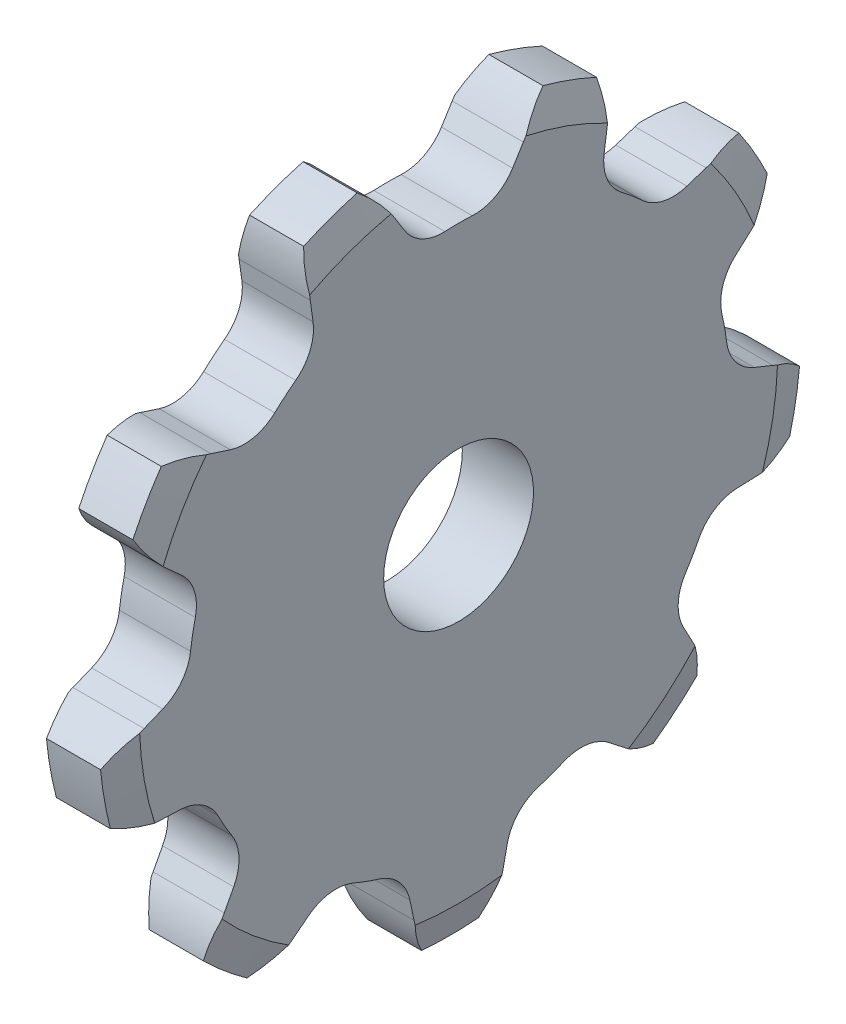
SolidWorks part; units mm, degrees
ref_plane "Plane1" through (0, 0, 0) normal (0, 0, 1) x (1, 0, 0)
ref_plane "Plane2" through (0, 0, 0) normal (0, 1, 0) x (1, 0, 0)
ref_plane "Plane3" through (0, 0, 0) normal (1, 0, 0) x (0, 0, -1)
sketch "Clipboard" plane through (0, 0, 0) normal (0, 1, 0) x (1, 0, 0)
  line L0 (0, 0) -> (75.2619, -11.9203)
  line L1 (-15, 0) -> (100, 0) construction
  line L2 (0, 0) -> (-2.1039, 2.3779)
  line L3 (0, 0) -> (-11.863, 4.5341)
  line L4 (0, 0) -> (8.5297, 1.351)
  line L5 (0, 0) -> (-71.3958, -26.6285)
  line L6 (0, 0) -> (-20.0029, -13.496)
  line L7 (-2.1039, 2.3779) -> (14.2981, 76.7917)
  line L8 (-76.2, 54.61) -> (-19.7358, 54.61)
  line L9 (-66.6514, 23.5599) -> (-48.0177, 27.5206)
  line L10 (-76.2, 71.12) -> (35.1969, 71.12)
  line L11 (0, 0) -> (-25.4, 0)
  line L12 (-76.2, 101.6) -> (-47.498, 101.6)
  circle A0 centre (0, 0) radius 19.05
  circle A1 centre (0, 0) radius 25.4
  circle A2 centre (0, 0) radius 25.4
  dimension "Num_teeth" = 9
  dimension "Pitch_radius" = 111.3969
  dimension "F" = 28.702
  dimension "H" = 19.05
  dimension "Thickness" = 24.13
sketch "BasProSke" plane through (0, 0, 0) normal (0, 1, 0) x (1, 0, 0)
  line L0 (-10, 0) -> (60, 0) construction
  line L1 (0, 0) -> (0, 108.2234)
  line L2 (0, 0) -> (24.13, 0)
  line L3 (24.13, 0) -> (24.13, 108.2234)
  line L4 (21.2344, 119.0299) -> (2.8956, 119.0299)
  line L5 (0, 108.2234) -> (2.8956, 119.0299)
  line L6 (24.13, 108.2234) -> (21.2344, 119.0299)
  dimension "Thickness" = 24.13
  dimension "Diameter" = 238.0598
  dimension "D1" = 15
  dimension "D2" = 15
revolve "Base-Revolve" add sketch "BasProSke" angle 360 about L0
sketch "TooCutSke" plane through (0, 0, 0) normal (1, 0, 0) x (0, 0, -1)
  line L0 (-18.3254, 98.6123) -> (-21.9596, 104.4283)
  line L1 (0, 0) -> (0, 107) construction
  line L2 (3.81, 0) -> (3.81, 141.3423) construction
  line L3 (18.3254, 98.6123) -> (21.9596, 104.4283)
  line L4 (44.0158, 120.9324) -> (48.3595, 132.8665)
  line L5 (3.81, 115.7694) -> (59.0408, 81.2573) construction
  line L6 (-44.0158, 120.9324) -> (-48.3595, 132.8665)
  arc A0 (4.6306, 91.4678) -> (-4.6306, 91.4678) centre (0, 0) ccw
  arc A1 (4.6306, 91.4678) -> (18.3254, 98.6123) centre (5.4011, 106.6883) ccw
  arc A2 (-4.6306, 91.4678) -> (-18.3254, 98.6123) centre (-5.4011, 106.6883) cw
  circle A3 centre (0, 0) radius 111.3969 construction
  circle A4 centre (3.81, 111.3318) radius 19.05 construction
  arc A5 (21.9596, 104.4283) -> (44.0158, 120.9324) centre (54.2702, 84.2383) cw
  arc A6 (-21.9596, 104.4283) -> (-44.0158, 120.9324) centre (-54.2702, 84.2383) ccw
  arc A7 (48.3595, 132.8665) -> (-48.3595, 132.8665) centre (0, 0) ccw
  dimension "Pitch_radius" = 111.3969
  dimension "R" = 15.24
  dimension "H" = 19.05
  dimension "Ag" = 64
  dimension "Angle" = 40
extrude "ToothCut" cut sketch "TooCutSke" along normal through all
pattern_circular "TeethCuts" count 9 every 40 about axis through (-10, 0, 0) along (1, 0, 0) of "ToothCut"
sketch "HubNeaOneSke" plane through (0, 0, 0) normal (-1, 0, 0) x (0, 0, 1)
  circle A0 centre (0, 0) radius 25.4
  dimension "Diameter" = 50.8
extrude "HubNearOne" [suppressed] add sketch "HubNeaOneSke" along normal blind 52.0701
sketch "HubNeaBotSke" plane through (0, 0, 0) normal (-1, 0, 0) x (0, 0, 1)
  circle A0 centre (0, 0) radius 25.4
  dimension "Diameter" = 50.8
extrude "HubNearBoth" [suppressed] add sketch "HubNeaBotSke" along normal blind 26.035
ref_plane "FarPln" through (24.13, 0, 0) normal (1, 0, 0) x (0, 0, -1)
sketch "HubFarSke" plane through (24.13, 0, 0) normal (1, 0, 0) x (0, 0, -1)
  circle A0 centre (0, 0) radius 25.4
  dimension "Diameter" = 50.8
extrude "HubFar" [suppressed] add sketch "HubFarSke" along normal blind 26.035
sketch "BorSke" plane through (0, 0, 0) normal (1, 0, 0) x (0, 0, -1)
  circle A0 centre (0, 0) radius 25.4
  dimension "Diameter" = 50.8
extrude "Bore" cut sketch "BorSke" along normal mid plane 152.4001
sketch "KeySke" plane through (0, 0, 0) normal (1, 0, 0) x (0, 0, -1)
  line L0 (-6.35, 0) -> (-6.35, 31.0642)
  line L1 (-6.35, 31.0642) -> (6.35, 31.0642)
  line L2 (6.35, 31.0642) -> (6.35, 0)
  line L3 (0, 0) -> (0, 34) construction
  line L4 (-6.35, 0) -> (6.35, 0)
  dimension "Width" = 12.7
extrude "Keyway" [suppressed] cut sketch "KeySke" along normal mid plane 152.4001
pattern_circular "Keyway2" [suppressed] count 2 every 90 about axis through (-10, 0, 0) along (1, 0, 0)
equation "\"Thickness@Clipboard\" = \"Width@Clipboard\" * 0.95"
equation "\"H@Clipboard\" = \"Diameter@Clipboard\" / 2.0"
equation "\"OAL@Clipboard\" = \"Thickness@Clipboard\""
equation "\"Pitch_radius@Clipboard\" = ( \"Pitch@Clipboard\" / 2.0) / sin(3.14159265 / \"Num_teeth@Clipboard\" )"
equation "\"MHD@Clipboard\" = (1.0 / tan(3.14159265 / \"Num_teeth@Clipboard\" ) - 0.05) * \"Pitch@Clipboard\" - \"F@Clipboard\""
equation "\"MHD@Clipboard\" = ((sgn( \"MHD@Clipboard\" - \"Hub_dia@Clipboard\" )-1)*( \"MHD@Clipboard\" - \"Hub_dia@Clipboard\" ))/-2+ \"Hub_dia@Clipboard\""
equation "\"OAL@Clipboard\" = ((sgn( \"OAL@Clipboard\" - \"Overall_len@Clipboard\" )+1)*( \"OAL@Clipboard\" - \"Overall_len@Clipboard\" ))/2 + \"Overall_len@Clipboard\" + 0.000002"
equation "\"Num_teeth@TeethCuts\" = int( \"Show_teeth@Clipboard\" ) + 1"
equation "\"Num_teeth@TeethCuts\" = ((sgn( \"Num_teeth@TeethCuts\" - \"Num_teeth@Clipboard\" )-1)*( \"Num_teeth@TeethCuts\" - \"Num_teeth@Clipboard\" ))/-2+ \"Num_teeth@Clipboard\""
equation "\"Num_teeth@TeethCuts\" = ((sgn( \"Num_teeth@TeethCuts\" - 2.0)+1)*( \"Num_teeth@TeethCuts\" - 2.0))/2 +2.0"
equation "\"Angle@TeethCuts\" = 360.0 / \"Num_teeth@Clipboard\""
equation "\"Pitch_radius@TooCutSke\" = \"Pitch_radius@Clipboard\""
equation "\"Cp@TooCutSke\" = 0.05 * \"Pitch@Clipboard\""
equation "\"Rt@TooCutSke\" = 0.5 * \"Pitch@Clipboard\""
equation "\"R@TooCutSke\"  = 0.8 * \"H@Clipboard\""
equation "\"Db@TooCutSke\" = \"Pitch_radius@Clipboard\" - \"H@Clipboard\" - 0.03"
equation "\"Ag@TooCutSke\" =  2.0 * \"Ap@Clipboard\" + 360.0 / \"Num_teeth@Clipboard\""
equation "\"H@TooCutSke\" = \"H@Clipboard\""
equation "\"Angle@TooCutSke\" =  360.0 / \"Num_teeth@Clipboard\""
equation "\"Wf@TooCutSke\" = 0.01 * \"Pitch@Clipboard\" * \"Num_teeth@Clipboard\""
equation "\"Wf@TooCutSke\" = ((sgn( \"Wf@TooCutSke\" - \"H@Clipboard\" * 0.8 )-1)*( \"Wf@TooCutSke\" - \"H@Clipboard\" * 0.8 ))/-2+ \"H@Clipboard\" * 0.8"
equation "\"Diameter@BasProSke\" = (1.0 / tan(3.14159265 / \"Num_teeth@Clipboard\" )) * \"Pitch@Clipboard\" + \"F@Clipboard\""
equation "\"Thickness@BasProSke\"  = \"Thickness@Clipboard\""
equation "\"G1@BasProSke\" =  \"Thickness@Clipboard\" * 0.12"
equation "\"G2@BasProSke\" =   \"Thickness@Clipboard\" * 0.12"
equation "\"MHD@Clipboard\" = ((sgn( \"MHD@Clipboard\" - \"Db@TooCutSke\" * 2.0  )-1)*( \"MHD@Clipboard\" - \"Db@TooCutSke\" * 2.0 ))/-2+ \"Db@TooCutSke\" * 2.0"
equation "\"Diameter@HubNeaOneSke\" = \"MHD@Clipboard\""
equation "\"Length@HubNearOne\" = \"OAL@Clipboard\" - \"Thickness@BasProSke\""
equation "\"Diameter@HubNeaBotSke\" = \"MHD@Clipboard\""
equation "\"Length@HubNearBoth\" = ( \"OAL@Clipboard\" - \"Thickness@BasProSke\" ) / 2.0"
equation "\"Thickness@FarPln\" = \"Thickness@BasProSke\""
equation "\"Diameter@HubFarSke\" = \"MHD@Clipboard\""
equation "\"Length@HubFar\" = ( \"OAL@Clipboard\" - \"Thickness@BasProSke\" ) / 2.0"
equation "\"D1@Bore\" = \"OAL@Clipboard\" * 2.0"
equation "\"D1@Keyway\" = \"OAL@Clipboard\" * 2.0"
equation "\"Offset@KeySke\" = \"T_dim@Clipboard\" - \"Diameter@BorSke\" / 2.0"
